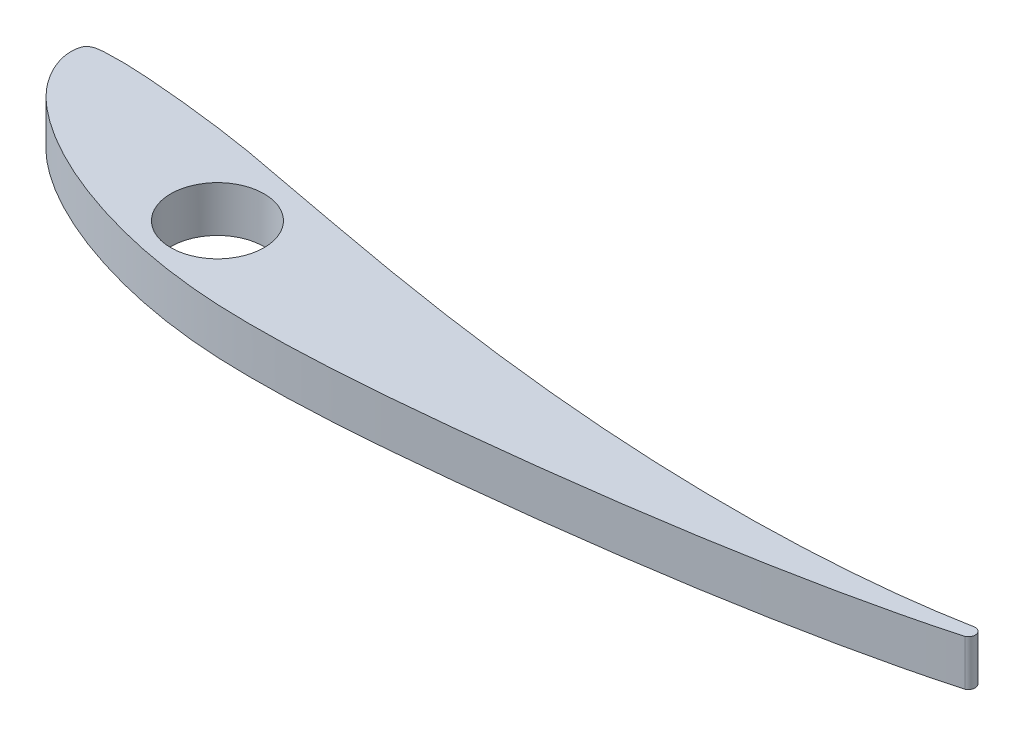
SolidWorks part; units mm, degrees
material "Balsa"
ref_plane "Front Plane" through (0, 0, 0) normal (0, 0, 1) x (1, 0, 0)
ref_plane "Top Plane" through (0, 0, 0) normal (0, 1, 0) x (1, 0, 0)
ref_plane "Right Plane" through (0, 0, 0) normal (1, 0, 0) x (0, 0, -1)
curve "Curve1"
  spline degree 3 poles (-3.7953, 0, -0.0099) (-3.8135, 0, 0.0025) (-3.7975, 0, -0.0094) (-3.7869, 0, -0.0198) (-3.7634, 0, -0.0415) (-3.7356, 0, -0.0646) (-3.6977, 0, -0.0879) (-3.6505, 0, -0.1105) (-3.5935, 0, -0.134) (-3.5268, 0, -0.1582) (-3.4508, 0, -0.1829) (-3.3657, 0, -0.2079) (-3.2722, 0, -0.233) (-3.1706, 0, -0.258) (-3.0616, 0, -0.2828) (-2.9459, 0, -0.3071) (-2.8241, 0, -0.331) (-2.697, 0, -0.354) (-2.5653, 0, -0.3761) (-2.4298, 0, -0.3971) (-2.2915, 0, -0.417) (-2.1511, 0, -0.4356) (-2.0096, 0, -0.4529) (-1.8684, 0, -0.4689) (-1.7284, 0, -0.4834) (-1.5908, 0, -0.496) (-1.4567, 0, -0.506) (-1.3267, 0, -0.5129) (-1.2016, 0, -0.5159) (-1.082, 0, -0.5155) (-0.9682, 0, -0.5097) (-0.8601, 0, -0.4978) (-0.7573, 0, -0.4811) (-0.6597, 0, -0.4593) (-0.5675, 0, -0.4338) (-0.481, 0, -0.4051) (-0.4006, 0, -0.3736) (-0.3268, 0, -0.3398) (-0.2599, 0, -0.3041) (-0.2001, 0, -0.2671) (-0.148, 0, -0.2293) (-0.1034, 0, -0.1913) (-0.0671, 0, -0.1529) (-0.0392, 0, -0.1144) (-0.0186, 0, -0.0769) (-0.0054, 0, -0.0412) (0.0009, 0, -0.0084) (-0.0003, 0, 0.0194) (-0.0075, 0, 0.0449) (-0.0341, 0, 0.0576) (-0.0699, 0, 0.0593) (-0.1188, 0, 0.0611) (-0.1803, 0, 0.0584) (-0.2538, 0, 0.0535) (-0.3383, 0, 0.0457) (-0.433, 0, 0.0352) (-0.5376, 0, 0.0216) (-0.6518, 0, 0.0027) (-0.7763, 0, -0.0211) (-0.9117, 0, -0.0469) (-1.0573, 0, -0.0742) (-1.2123, 0, -0.1018) (-1.3754, 0, -0.1287) (-1.5454, 0, -0.154) (-1.7209, 0, -0.1767) (-1.9002, 0, -0.1962) (-2.0817, 0, -0.2116) (-2.2636, 0, -0.2225) (-2.4439, 0, -0.2285) (-2.6207, 0, -0.2293) (-2.792, 0, -0.2247) (-2.9559, 0, -0.215) (-3.1104, 0, -0.2002) (-3.2537, 0, -0.1809) (-3.3838, 0, -0.1577) (-3.4993, 0, -0.1313) (-3.598, 0, -0.103) (-3.6788, 0, -0.0729) (-3.7364, 0, -0.0453) (-3.7789, 0, -0.0198) (-3.7953, 0, -0.0099) (-3.8135, 0, 0.0025) (-3.7975, 0, -0.0094) knots -0.009748 -0.004147 -0.001 0 0.00098 0.003649 0.007483 0.012095 0.017526 0.024052 0.031783 0.040678 0.05071 0.061833 0.073989 0.087118 0.101145 0.115991 0.13157 0.147788 0.164551 0.181758 0.199312 0.217095 0.23499 0.252857 0.270541 0.287887 0.304773 0.321101 0.336806 0.3518 0.366031 0.379616 0.392653 0.40517 0.417172 0.428604 0.439419 0.449597 0.459102 0.467908 0.475988 0.483309 0.489875 0.495803 0.501149 0.505903 0.510047 0.513579 0.516447 0.51935 0.523823 0.529974 0.537716 0.546968 0.557637 0.56962 0.582804 0.597247 0.613135 0.630444 0.649056 0.668822 0.689595 0.71119 0.733427 0.756094 0.778989 0.80189 0.824567 0.846792 0.868338 0.888978 0.908492 0.926659 0.943286 0.958169 0.971136 0.981956 0.990252 0.995853 0.999 1 1.00098 1.003649 1.007483 periodic
sketch "Sketch1" plane through (0, 0, 0) normal (0, 1, 0) x (1, 0, 0)
  line L0 (150, 0) -> (0, 0) construction
  line L1 (0, -0.0038) -> (0, 31241.5392) construction
  spline S1 degree 3 poles (149.5079, -0.3714) (150.1359, 0.0969) (149.4197, -0.3897) (148.7771, -0.7786) (147.1043, -1.7836) (144.8353, -2.8707) (141.6549, -4.0588) (137.7688, -5.1723) (133.2225, -6.2132) (128.0998, -7.1299) (122.4608, -7.8917) (116.3789, -8.4765) (109.9265, -8.8619) (103.1812, -9.043) (96.2202, -9.0156) (89.1212, -8.7815) (81.9612, -8.3539) (74.815, -7.7495) (67.7544, -6.9843) (60.846, -6.0927) (54.1519, -5.1006) (47.7299, -4.0446) (41.6298, -2.9598) (35.8964, -1.8873) (30.5658, -0.8714) (25.6639, 0.0621) (21.1664, 0.8062) (17.0513, 1.3384) (13.3206, 1.7532) (9.9925, 2.0595) (7.1011, 2.2505) (4.6785, 2.3541) (2.7521, 2.2857) (1.344, 2.2153) (0.2968, 1.7167) (0.0154, 0.7128) (-0.032, -0.3816) (0.2161, -1.6755) (0.7365, -3.0773) (1.5481, -4.5536) (2.6468, -6.0709) (4.0769, -7.5826) (5.8318, -9.0754) (7.8858, -10.5656) (10.2383, -12.0217) (12.8744, -13.424) (15.7798, -14.7564) (18.9451, -15.9919) (22.3507, -17.1239) (25.9822, -18.1259) (29.824, -18.9801) (33.8724, -19.6391) (38.1281, -20.1047) (42.6087, -20.3336) (47.3157, -20.3444) (52.2405, -20.2257) (57.3578, -19.953) (62.6391, -19.5573) (68.0544, -19.0596) (73.5654, -18.4879) (79.1274, -17.8529) (84.6942, -17.1705) (90.2214, -16.436) (95.6689, -15.6517) (101.0019, -14.8238) (106.1858, -13.9507) (111.1907, -13.0437) (115.9852, -12.104) (120.5412, -11.1432) (124.8309, -10.1662) (128.8288, -9.1792) (132.5118, -8.1893) (135.8597, -7.2055) (138.8538, -6.2326) (141.4784, -5.2789) (143.7214, -4.3511) (145.5793, -3.4622) (147.0733, -2.5452) (148.1654, -1.6356) (149.091, -0.7807) (149.5079, -0.3714) (150.1359, 0.0969) (149.4197, -0.3897) knots -0.007483 -0.003649 -0.00098 0 0.001 0.004147 0.009748 0.018044 0.028864 0.041831 0.056714 0.073341 0.091508 0.111022 0.131662 0.153208 0.175433 0.19811 0.221011 0.243906 0.266573 0.28881 0.310405 0.331178 0.350944 0.369556 0.386865 0.402753 0.417196 0.43038 0.442363 0.453032 0.462284 0.470026 0.476177 0.48065 0.483553 0.486421 0.489953 0.494097 0.498851 0.504197 0.510125 0.516691 0.524012 0.532092 0.540898 0.550403 0.560581 0.571396 0.582828 0.59483 0.607347 0.620384 0.633969 0.6482 0.663194 0.678899 0.695227 0.712113 0.729459 0.747143 0.76501 0.782905 0.800688 0.818242 0.835449 0.852212 0.86843 0.884009 0.898855 0.912882 0.926011 0.938167 0.94929 0.959322 0.968217 0.975948 0.982474 0.987905 0.992517 0.996351 0.99902 1 1.001 1.004147 1.009748 only from (150, 0) to (150, 0)
  dimension "D1" = 150
extrude "Boss-Extrude1" add sketch "Sketch1" along normal blind 3.175 and the other way blind 3.175
sketch "Sketch3" plane through (0, 3.175, 0) normal (0, 1, 0) x (1, 0, 0)
  line L0 (-1000, 0) -> (49000, 0) construction
  line L1 (30.48, -10.16) -> (30.48, 0) construction
  circle A0 centre (30.48, -10.16) radius 6.477
  dimension "D1" = 12.954
  dimension "D3" = 30.48
  dimension "D4" = 10.16
extrude "Cut-Extrude2" cut sketch "Sketch3" against normal through all both and the other way through all
sketch "Sketch5" plane through (0, 3.175, 0) normal (0, 1, 0) x (1, 0, 0)
  line L0 (132.234, -8.2524) -> (157.14, -4.1233)
  line L1 (157.14, -4.1233) -> (151.4197, 7.3962)
  line L2 (151.4197, 7.3962) -> (131.4696, -6.514)
  arc A0 (131.4696, -6.514) -> (132.234, -8.2524) centre (131.8518, -7.3832) cw
  spline S0 degree 3 poles (149.5079, -0.3714) (150.1359, 0.0969) (149.4197, -0.3897) (148.7771, -0.7786) (147.1043, -1.7836) (144.8353, -2.8707) (141.6549, -4.0588) (137.7688, -5.1723) (133.2225, -6.2132) (128.0998, -7.1299) (122.4608, -7.8917) (116.3789, -8.4765) (109.9265, -8.8619) (103.1812, -9.043) (96.2202, -9.0156) (89.1212, -8.7815) (81.9612, -8.3539) (74.815, -7.7495) (67.7544, -6.9843) (60.846, -6.0927) (54.1519, -5.1006) (47.7299, -4.0446) (41.6298, -2.9598) (35.8964, -1.8873) (30.5658, -0.8714) (25.6639, 0.0621) (21.1664, 0.8062) (17.0513, 1.3384) (13.3206, 1.7532) (9.9925, 2.0595) (7.1011, 2.2505) (4.6785, 2.3541) (2.7521, 2.2857) (1.344, 2.2153) (0.2968, 1.7167) (0.0154, 0.7128) (-0.032, -0.3816) (0.2161, -1.6755) (0.7365, -3.0773) (1.5481, -4.5536) (2.6468, -6.0709) (4.0769, -7.5826) (5.8318, -9.0754) (7.8858, -10.5656) (10.2383, -12.0217) (12.8744, -13.424) (15.7798, -14.7564) (18.9451, -15.9919) (22.3507, -17.1239) (25.9822, -18.1259) (29.824, -18.9801) (33.8724, -19.6391) (38.1281, -20.1047) (42.6087, -20.3336) (47.3157, -20.3444) (52.2405, -20.2257) (57.3578, -19.953) (62.6391, -19.5573) (68.0544, -19.0596) (73.5654, -18.4879) (79.1274, -17.8529) (84.6942, -17.1705) (90.2214, -16.436) (95.6689, -15.6517) (101.0019, -14.8238) (106.1858, -13.9507) (111.1907, -13.0437) (115.9852, -12.104) (120.5412, -11.1432) (124.8309, -10.1662) (128.8288, -9.1792) (132.5118, -8.1893) (135.8597, -7.2055) (138.8538, -6.2326) (141.4784, -5.2789) (143.7214, -4.3511) (145.5793, -3.4622) (147.0733, -2.5452) (148.1654, -1.6356) (149.091, -0.7807) (149.5079, -0.3714) (150.1359, 0.0969) (149.4197, -0.3897) knots -0.007483 -0.003649 -0.00098 0 0.001 0.004147 0.009748 0.018044 0.028864 0.041831 0.056714 0.073341 0.091508 0.111022 0.131662 0.153208 0.175433 0.19811 0.221011 0.243906 0.266573 0.28881 0.310405 0.331178 0.350944 0.369556 0.386865 0.402753 0.417196 0.43038 0.442363 0.453032 0.462284 0.470026 0.476177 0.48065 0.483553 0.486421 0.489953 0.494097 0.498851 0.504197 0.510125 0.516691 0.524012 0.532092 0.540898 0.550403 0.560581 0.571396 0.582828 0.59483 0.607347 0.620384 0.633969 0.6482 0.663194 0.678899 0.695227 0.712113 0.729459 0.747143 0.76501 0.782905 0.800688 0.818242 0.835449 0.852212 0.86843 0.884009 0.898855 0.912882 0.926011 0.938167 0.94929 0.959322 0.968217 0.975948 0.982474 0.987905 0.992517 0.996351 0.99902 1 1.001 1.004147 1.009748 only from (150, 0) to (150, 0) construction
extrude "Cut-Extrude3" cut sketch "Sketch5" against normal through all both and the other way through all
